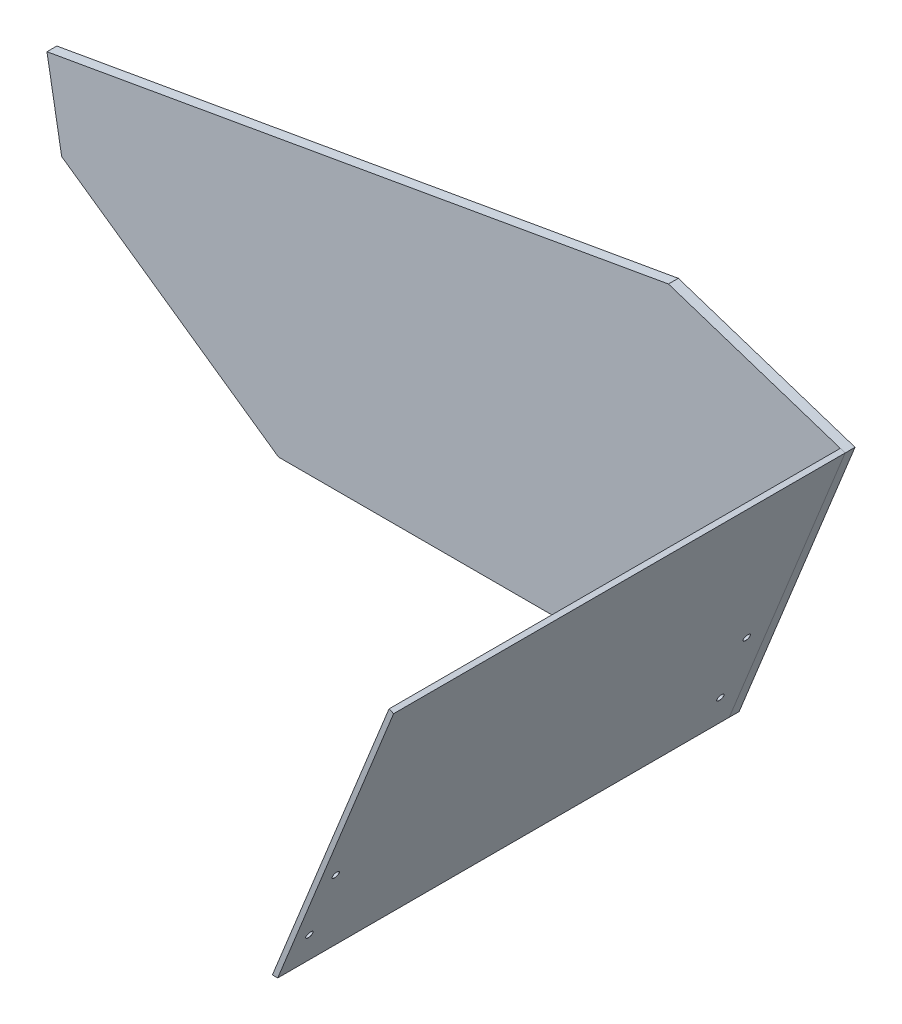
SolidWorks part; units mm, degrees
material "Melamine"
ref_plane "Front Plane" through (0, 0, 0) normal (0, 0, 1) x (1, 0, 0)
ref_plane "Top Plane" through (0, 0, 0) normal (0, 1, 0) x (1, 0, 0)
ref_plane "Right Plane" through (0, 0, 0) normal (1, 0, 0) x (0, 0, -1)
ref_axis "Axis1" through (0, 0, -14.8175) along (0, 0, 1)
sketch "Sketch1" plane through (0, 0, 0) normal (0, 0, 1) x (1, 0, 0)
  line L0 (-140, 0) -> (140, 0) construction
  line L1 (-140, 0) -> (-303.8304, 114.7153) construction
  line L4 (-151.0709, 0) -> (-307.4726, 109.5137) construction
  line L5 (-307.4726, 109.5137) -> (-303.8304, 114.7153) construction
  line L11 (140, 0) -> (143.4243, 0)
  line L12 (140, 0) -> (214.9213, 185.4368) construction
  line L14 (143.4243, 0) -> (217.8651, 184.2474)
  line L15 (217.8651, 184.2474) -> (214.9213, 185.4368)
  line L16 (214.9213, 185.4368) -> (140, 0)
  line L17 (-140, 0) -> (-151.0709, 0) construction
  point P4 (0, 0)
  dimension "D1" = 35
  dimension "D2" = 280
  dimension "D4" = 200
  dimension "D6" = 6.35
  dimension "D7" = 68
  dimension "D8" = 200
  dimension "D9" = 3.175
extrude "Boss-Extrude1" add sketch "Sketch1" along normal blind 290
sketch "Sketch2" plane through (0, 0, 0) normal (0, 0, 1) x (1, 0, 0)
  line L1 (-294.7779, 151.108) -> (104.3699, 221.4886)
  line L3 (143.4243, 0) -> (-146.0709, 0)
  line L4 (-146.0709, 0) -> (-285.3267, 97.508) construction
  line L5 (143.4243, 0) -> (217.8651, 184.2474)
  line L7 (-285.3267, 97.508) -> (-294.7779, 151.108)
  line L8 (-285.3267, 97.508) -> (-281.6845, 102.7096) construction
  line L9 (217.8651, 184.2474) -> (104.3699, 221.4886)
  line L10 (143.4243, 0) -> (104.3699, 221.4886) construction
  line L11 (-285.3267, 97.508) -> (-146.0709, 0)
  line L13 (-146.0709, 0) -> (-135, 0) construction
  line L14 (-285.3267, 97.508) -> (-146.0709, 0) construction
  line L15 (-281.6845, 102.7096) -> (-135, 0) construction
  dimension "D1" = 10
  dimension "D2" = 200
  dimension "D3" = 6.35
  dimension "D4" = 35
  dimension "D5" = 170
  dimension "D6" = 275
extrude "Boss-Extrude2" add sketch "Sketch2" against normal blind 6.35 separate body
ref_plane "HOLDING PLANE" through (0, 0, 0) normal (0.9848, 0.1736, 0) x (0, 0, 1)
ref_point "Walls Center"
hole_wizard "M4 Clearance Hole1" positions "Sketch3" profile "Sketch4" hole size "M4" standard "ANSI Metric" end condition through all
sketch "Sketch3" plane through (123.2976, -49.8155, 0) normal (0.9272, -0.3746, 0) x (0, 0, -1)
  point P0 (-279, 123.7277)
  point P3 (-279, 78.7277)
  point P6 (-15, 123.7277)
  point P9 (-15, 78.7277)
sketch "Sketch4" plane through (169.6468, 64.9029, 279) normal (0, 0, 1) x (0.3746, 0.9272, 0)
  line L0 (0, 0) -> (0, 489.2651)
  line L1 (0, 489.2651) -> (2.25, 489.2651)
  line L2 (2.25, 489.2651) -> (2.25, 0.025)
  line L3 (2.25, 0.025) -> (2.275, 0)
  line L5 (2.275, 0) -> (0, 0)
  line L6 (-2.25, 0.025) -> (-2.275, 0) construction
  line L11 (0, -6.35) -> (0, 107.95) construction
  dimension "Thru Hole Dia." = 4.5
  dimension "Thru Hole Depth" = 489.2651
  dimension "Near C'Sink Dia." = 4.55
  dimension "Near C'Sink Angle" = 90
